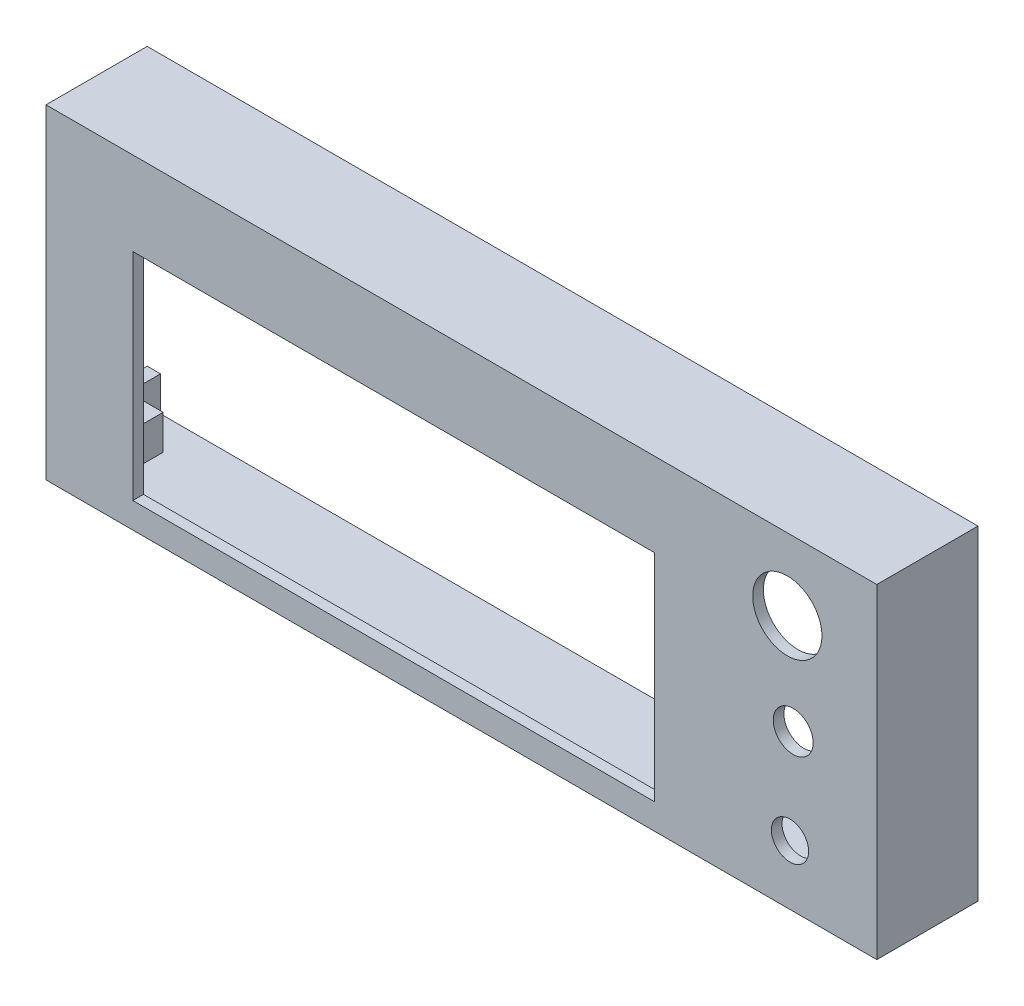
SolidWorks part; units mm, degrees
material "ABS"
ref_plane "Front Plane" through (0, 0, 0) normal (0, 0, 1) x (1, 0, 0)
ref_plane "Top Plane" through (0, 0, 0) normal (0, 1, 0) x (1, 0, 0)
ref_plane "Right Plane" through (0, 0, 0) normal (1, 0, 0) x (0, 0, -1)
sketch "Sketch1" plane through (0, 0, 0) normal (0, 0, 1) x (1, 0, 0)
  line L0 (-93, 10.5) -> (-78, 10.5)
  line L1 (93, 30.5) -> (-93, 30.5)
  line L2 (93, 30.5) -> (93, 10.5)
  line L3 (78, -30.5) -> (-78, -30.5)
  line L4 (-93, 30.5) -> (-93, 10.5)
  line L5 (93, 30.5) -> (-93, -30.5) construction
  line L6 (93, -30.5) -> (-93, 30.5) construction
  line L7 (-78, 10.5) -> (-78, -30.5)
  line L8 (93, 10.5) -> (78, 10.5)
  line L9 (78, 10.5) -> (78, -30.5)
  point P0 (0, 0)
  dimension "D1" = 186
  dimension "D2" = 61
  dimension "D3" = 20
  dimension "D4" = 15
  dimension "D5" = 15
  dimension "D6" = 93
  dimension "D7" = 30.5
  dimension "D8" = 61
extrude "Boss-Extrude1" add sketch "Sketch1" along normal blind 24
sketch "Sketch2" plane through (0, 0, 0) normal (0, 0, -1) x (-1, 0, 0)
  line L0 (-78, -30.5) -> (-78, 10.5) construction
  line L1 (75.5, -28) -> (-75.5, -28)
  line L2 (75.5, -28) -> (75.5, 28)
  line L3 (75.5, 28) -> (-75.5, 28)
  line L4 (-75.5, -28) -> (-75.5, 28)
  line L5 (75.5, -28) -> (-75.5, 28) construction
  line L6 (75.5, 28) -> (-75.5, -28) construction
  line L7 (-93, 30.5) -> (93, 30.5) construction
  point P0 (0, 0)
  dimension "D1" = 2.5
  dimension "D2" = 2.5
extrude "Cut-Extrude1" cut sketch "Sketch2" against normal blind 22
sketch "Sketch3" plane through (0, 0, 0) normal (0, 0, -1) x (-1, 0, 0)
  line L1 (78, 30.5) -> (-78, 30.5)
  line L2 (78, 30.5) -> (78, -30.5)
  line L3 (78, -30.5) -> (-78, -30.5)
  line L4 (-78, 30.5) -> (-78, -30.5)
  line L5 (78, 30.5) -> (-78, -30.5) construction
  line L6 (78, -30.5) -> (-78, 30.5) construction
  point P0 (0, 0)
extrude "Cut-Extrude2" cut sketch "Sketch3" against normal blind 5
sketch "Sketch4" plane through (0, 0, 24) normal (0, 0, 1) x (1, 0, 0)
  line L0 (-78, 10.5) -> (-78, -30.5) construction
  line L1 (-61.7, -25.7) -> (36.3, -25.7)
  line L2 (-61.7, -25.7) -> (-61.7, 14.8)
  line L3 (-61.7, 14.8) -> (36.3, 14.8)
  line L4 (36.3, -25.7) -> (36.3, 14.8)
  line L5 (-78, -30.5) -> (78, -30.5) construction
  line L7 (93, 30.5) -> (-93, 30.5) construction
  line L9 (78, -30.5) -> (78, 10.5) construction
  circle A0 centre (61.2, 17) radius 6.5
  circle A1 centre (62.3, -1.25) radius 3.75
  circle A2 centre (61.7, -19.3) radius 3.5
  dimension "D5" = 13
  dimension "D6" = 7.5
  dimension "D7" = 7
  dimension "D1" = 98
  dimension "D2" = 40.5
  dimension "D3" = 16.3
  dimension "D4" = 4.8
  dimension "D8" = 16.8
  dimension "D9" = 18.25
  dimension "D10" = 11.2
  dimension "D11" = 13.5
  dimension "D12" = 15.7
  dimension "D13" = 16.3
extrude "Cut-Extrude3" cut sketch "Sketch4" against normal blind 4
hole_wizard "CBORE for M4 Hex Socket Head Cap Screw1" positions "Sketch5" profile "Sketch6" counterbore size "M4" standard "DIN" end condition through all
sketch "Sketch5" plane through (0, 0, 24) normal (0, 0, 1) x (1, 0, 0)
  line L0 (-93, 10.5) -> (-78, 10.5) construction
  line L1 (-93, 30.5) -> (-93, 10.5) construction
  point P0 (-85, 20.5)
  point P2 (85, 20.3761)
  dimension "D1" = 10
  dimension "D2" = 170
  dimension "D3" = 8
sketch "Sketch6" plane through (-85, 20.5, 24) normal (1, 0, 0) x (0, -1, 0)
  line L0 (0, 0) -> (0, 24)
  line L1 (0, 24) -> (2.25, 24)
  line L3 (2.25, 24) -> (2.25, 4.4)
  line L4 (2.25, 4.4) -> (4, 4.4)
  line L5 (4, 4.4) -> (4, 0)
  line L7 (4, 0) -> (0, 0)
  line L11 (0, -6.35) -> (0, 107.95) construction
  dimension "Thru Hole Dia." = 4.5
  dimension "Thru Hole Depth" = 24
  dimension "C'Bore Dia." = 8
  dimension "C'Bore Depth" = 4.4
sketch "Sketch7" plane through (0, 0, 22) normal (0, 0, -1) x (-1, 0, 0)
  line L1 (-75.5, 28) -> (-69, 28)
  line L2 (-75.5, 28) -> (-75.5, 21.5)
  line L3 (-75.5, 21.5) -> (-69, 21.5)
  line L4 (-69, 28) -> (-69, 21.5)
  line L5 (-75.5, -28) -> (-69, -28)
  line L6 (-75.5, -28) -> (-75.5, -21.5)
  line L7 (-75.5, -21.5) -> (-69, -21.5)
  line L8 (-69, -28) -> (-69, -21.5)
  line L9 (75.5, 28) -> (69, 28)
  line L10 (75.5, 28) -> (75.5, 21.5)
  line L11 (75.5, 21.5) -> (69, 21.5)
  line L12 (69, 28) -> (69, 21.5)
  line L13 (75.5, -28) -> (69, -28)
  line L14 (75.5, -28) -> (75.5, -21.5)
  line L15 (75.5, -21.5) -> (69, -21.5)
  line L16 (69, -28) -> (69, -21.5)
  dimension "D1" = 6.5
  dimension "D2" = 6.5
  dimension "D3" = 6.5
  dimension "D4" = 6.5
  dimension "D5" = 6.5
  dimension "D6" = 6.5
  dimension "D7" = 6.5
  dimension "D8" = 6.5
extrude "Boss-Extrude2" add sketch "Sketch7" along normal blind 11
hole_wizard "Ø2.0mm Dowel Hole1" positions "Sketch8" profile "Sketch9" hole size "Ø2.0" standard "DIN"
sketch "Sketch8" plane through (0, 0, 11) normal (0, 0, -1) x (-1, 0, 0)
  point P0 (-72.25, 24.75)
  point P2 (-72.25, -24.75)
  point P4 (72.25, 24.75)
  point P6 (72.25, -24.75)
  dimension "D1" = 49.5
  dimension "D2" = 49.5
  dimension "D3" = 144.5
  dimension "D4" = 144.5
  dimension "D5" = 72.25
  dimension "D6" = 24.75
  dimension "D7" = 24.75
  dimension "D8" = 72.25
sketch "Sketch9" plane through (72.25, 24.75, 11) normal (1, 0, 0) x (0, 1, 0)
  line L0 (0, 0) -> (0, 8.6009)
  line L1 (0, 8.6009) -> (1, 8)
  line L2 (1, 8) -> (1, 0)
  line L5 (1, 0) -> (0, 0)
  line L10 (0, 8.6009) -> (-1, 8) construction
  line L11 (0, -6.35) -> (0, 107.95) construction
  dimension "Hole Dia." = 2
  dimension "Hole Depth" = 8
  dimension "Drill Angle" = 118
sketch "Sketch13" plane through (0, 0, 0) normal (0, 0, -1) x (-1, 0, 0)
  line L1 (-93, 30.5) -> (-78, 30.5)
  line L2 (-93, 30.5) -> (-93, 10.5)
  line L3 (-93, 10.5) -> (-78, 10.5)
  line L4 (-78, 30.5) -> (-78, 10.5)
  line L5 (93, 30.5) -> (78, 30.5)
  line L6 (93, 30.5) -> (93, 10.5)
  line L7 (93, 10.5) -> (78, 10.5)
  line L8 (78, 30.5) -> (78, 10.5)
extrude "Cut-Extrude6" cut sketch "Sketch13" against normal blind 24
sketch "Sketch14" plane through (-78, 0, 0) normal (-1, 0, 0) x (0, 0, 1)
  line L0 (5, -30.5) -> (5, 30.5) construction
  line L1 (5, -21.5) -> (11, -21.5)
  line L2 (5, -21.5) -> (5, 9.5)
  line L3 (5, 9.5) -> (11, 9.5)
  line L4 (11, -21.5) -> (11, 9.5)
  line L5 (24, -30.5) -> (5, -30.5) construction
  dimension "D1" = 31
  dimension "D2" = 6
  dimension "D3" = 9
extrude "Cut-Extrude7" cut sketch "Sketch14" against normal blind 3
